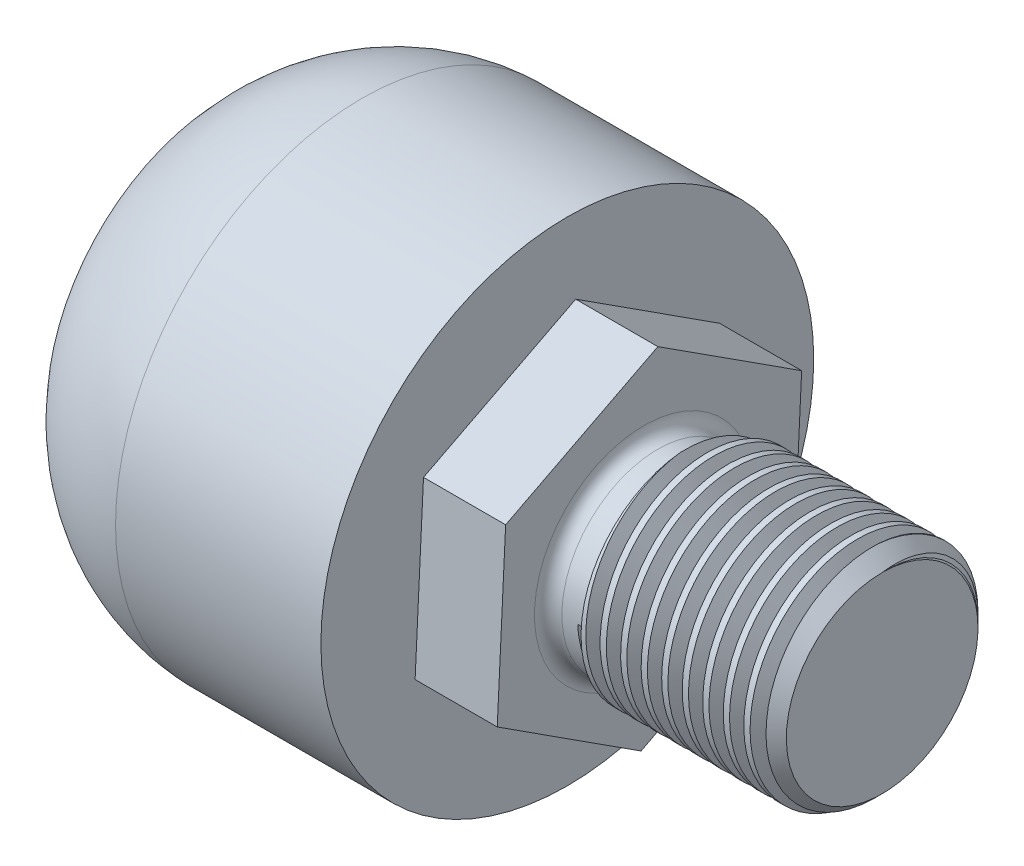
SolidWorks part; units mm, degrees
material "AISI 321 Tavlı Paslanmaz Çelik (SS)"
ref_plane "Ön Düzlem" through (0, 0, 0) normal (0, 0, 1) x (1, 0, 0)
ref_plane "Üst Düzlem" through (0, 0, 0) normal (0, 1, 0) x (1, 0, 0)
ref_plane "Sağ Düzlem" through (0, 0, 0) normal (1, 0, 0) x (0, 0, -1)
sketch "Çizim1" plane through (0, 0, 0) normal (0, 0, 1) x (1, 0, 0)
  line L0 (-25, 13) -> (-23.9, 11.25)
  line L1 (-22.4, 10.75) -> (-23.9, 11.25)
  line L2 (-21.9133, 10.75) -> (-22.4, 10.75)
  line L3 (-14.5352, 13.65) -> (-15, 14)
  line L4 (-8.9, 13.75) -> (-14.5352, 13.65)
  line L5 (-8.9, 13.75) -> (-8.0352, 12)
  line L6 (-0.1535, 1.75) -> (-0.1535, 0)
  line L7 (0, 18) -> (0, 0)
  line L8 (0, 18) -> (-15, 18)
  line L9 (-0.1535, 0) -> (0, 0)
  arc A0 (-15, 18) -> (-25, 13) centre (-14.3013, 4.1026) ccw
  arc A1 (-15, 14) -> (-21.9133, 10.75) centre (-13.414, 1.6483) ccw
  arc A2 (-0.1535, 1.75) -> (-8.0352, 12) centre (-13.2264, -0.147) ccw
revolve "Döndür1" add sketch "Çizim1" angle 360 about L9
sketch "Çizim2" plane through (0, 0, 0) normal (1, 0, 0) x (0, 0, -1)
  line L1 (-0.6134, -12.4846) -> (10.5053, -6.7735)
  line L2 (10.5053, -6.7735) -> (11.1186, 5.7111)
  line L3 (11.1186, 5.7111) -> (0.6134, 12.4846)
  line L4 (0.6134, 12.4846) -> (-10.5053, 6.7735)
  line L5 (-10.5053, 6.7735) -> (-11.1186, -5.7111)
  line L6 (-11.1186, -5.7111) -> (-0.6134, -12.4846)
  circle A0 centre (0, 0) radius 10.825 construction
extrude "Yükseklik-Ekstrüzyon1" add sketch "Çizim2" along normal blind 6
sketch "Çizim3" plane through (6, 0, 0) normal (1, 0, 0) x (0, 0, -1)
  circle A0 centre (0, 0) radius 8
extrude "Yükseklik-Ekstrüzyon2" add sketch "Çizim3" along normal blind 17
chamfer "Pah1" distance 1 angle 45 1 edges at (23, 0, -8)
sketch "Çizim4" plane through (23, 0, 0) normal (1, 0, 0) x (0, 0, -1)
  circle A0 centre (0, 0) radius 8 construction
  circle A1 centre (0, 0) radius 8
curve "Helis/Spiral1" pitch 1.5 height 14.625 radius 8 centre (23, 0, 0) axis (-1, 0, 0) start towards (0, 1, 0)
sketch "Çizim5" plane through (0, 0, 0) normal (0, 0, 1) x (1, 0, 0)
  line L0 (23, 7) -> (22.09, 8.7481)
  line L1 (22.09, 8.7481) -> (23.91, 8.7481)
  line L2 (23.91, 8.7481) -> (23, 7)
  line L4 (23, -7) -> (23, 7) construction
  dimension "D1" = 55
  dimension "D2" = 27.5
  dimension "D3" = 1
sweep "Kes-Süpür1" cut profiles "Çizim5" path "Helis/Spiral1"
sketch "Çizim6" plane through (6, 0, 0) normal (1, 0, 0) x (0, 0, -1)
  circle A0 centre (-0.3975, 0) radius 7
  circle A1 centre (-0.3975, 0) radius 14.6273
extrude "Kes-Ekstrüzyon1" cut sketch "Çizim6" along normal blind 3
fillet "Radyus1" radius 1 1 edges at (6, 0, -6.6025)
